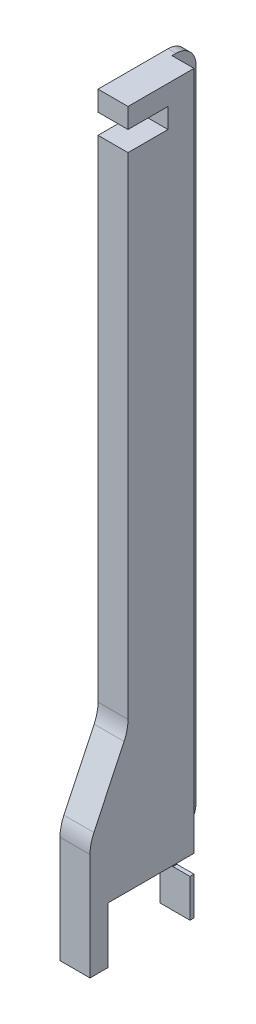
SolidWorks part; units mm, degrees
ref_plane "정면" through (0, 0, 0) normal (0, 0, 1) x (1, 0, 0)
ref_plane "윗면" through (0, 0, 0) normal (0, 1, 0) x (1, 0, 0)
ref_plane "우측면" through (0, 0, 0) normal (1, 0, 0) x (0, 0, -1)
sketch "스케치1" plane through (0, 0, 0) normal (0, 0, 1) x (1, 0, 0)
  line L0 (-318.5049, 0) -> (318.5049, 0) construction
  line L1 (0, 0) -> (0, -258.8265) construction
  line L2 (-168, 0) -> (168, 0)
  line L3 (-168, -20) -> (168, -20)
  line L4 (168, -20) -> (168, 0) construction
  line L5 (168, -20) -> (168, -340)
  line L6 (172, -340) -> (172, 0)
  line L7 (168, 0) -> (183, 0)
  line L8 (183, 0) -> (183, -340)
  line L9 (183, -340) -> (168, -340)
  line L10 (-168, -20) -> (-168, 0) construction
  line L11 (-183, -340) -> (-168, -340)
  line L12 (-183, 0) -> (-183, -340)
  line L13 (-168, 0) -> (-183, 0)
  line L14 (-172, -340) -> (-172, 0)
  line L15 (-168, -20) -> (-168, -340)
  line L16 (168, -20) -> (168, 0)
  line L17 (-168, -20) -> (-168, 0)
  point P14 (0, -20)
  dimension "D1" = 168
  dimension "D2" = 20
  dimension "D3" = 4
  dimension "D4" = 340
  dimension "D5" = 15
extrude "보스-돌출1" add sketch "스케치1" along normal blind 26 contours L3 L5 L9 L8 L7 L2 L13 L12 L11 L15
extrude "보스-돌출2" add sketch "스케치1<4>" against normal blind 19 contours L16 L5 L9 L6 L7 | L15 L17 L13 L14 L11 region at (-170, -170, 0) region at (170, -170, 0)
sketch "스케치1<4>" plane through (0, 0, 0) normal (0, 0, 1) x (1, 0, 0) same geometry as "스케치1"
fillet "필렛1" radius 10 4 edges at (-170, 0, -19) (170, 0, -19) (170, -340, -19) (-170, -340, -19)
sketch "스케치2" plane through (172, 0, 0) normal (1, 0, 0) x (0, 0, -1)
  line L0 (14, -340) -> (14, 0)
  line L1 (12, 0) -> (12, -340)
  line L4 (19, -330) -> (19, -10)
  line L5 (9, 0) -> (0, 0)
  line L6 (0, 0) -> (0, -340)
  line L7 (0, -340) -> (9, -340)
  line L8 (19, -330) -> (19, -10)
  line L9 (9, 0) -> (0, 0)
  line L10 (0, 0) -> (0, -340)
  line L11 (0, -340) -> (9, -340)
  arc A2 (19, -10) -> (9, 0) centre (9, -10) ccw
  arc A3 (9, -340) -> (19, -330) centre (9, -330) ccw
  arc A4 (19, -10) -> (9, 0) centre (9, -10) ccw
  arc A5 (9, -340) -> (19, -330) centre (9, -330) ccw
  dimension "D2" = 5
  dimension "D3" = 2
  dimension "D1" = 0
sketch "스케치3" plane through (168, 0, 0) normal (-1, 0, 0) x (0, 0, 1)
  line L0 (-12, 0) -> (-12, -340) construction
  line L1 (-14, -340) -> (-14, 0) construction
  line L2 (-12, 0) -> (-12, -340)
  line L3 (-14, -340) -> (-14, 0)
  line L4 (-19, -10) -> (-19, -330)
  line L5 (0, 0) -> (-9, 0)
  line L6 (0, -340) -> (0, 0)
  line L7 (-9, -340) -> (0, -340)
  line L8 (-19, -10) -> (-19, -330)
  line L9 (0, 0) -> (-9, 0)
  line L10 (0, -340) -> (0, 0)
  line L11 (-9, -340) -> (0, -340)
  arc A2 (-9, 0) -> (-19, -10) centre (-9, -10) ccw
  arc A3 (-19, -330) -> (-9, -340) centre (-9, -330) ccw
  arc A4 (-9, 0) -> (-19, -10) centre (-9, -10) ccw
  arc A5 (-19, -330) -> (-9, -340) centre (-9, -330) ccw
  dimension "D1" = 0
sketch "스케치5" plane through (0, 0, 0) normal (0, 1, 0) x (1, 0, 0)
  line L0 (-7, 0) -> (-7, -26)
  line L1 (7, 0) -> (7, -26)
  line L2 (-168, 0) -> (-168, -6)
  line L3 (-168, -6) -> (-7, -6)
  line L4 (7, -6) -> (168, -6)
  line L5 (168, -6) -> (168, 0)
  line L12 (-168, 0) -> (-168, 9)
  line L13 (-168, 9) -> (-172, 9)
  line L14 (-172, 9) -> (-172, 0)
  line L15 (-172, 0) -> (-183, 0)
  line L16 (-183, 0) -> (-183, -26)
  line L17 (-183, -26) -> (183, -26)
  line L18 (183, -26) -> (183, 0)
  line L19 (183, 0) -> (172, 0)
  line L20 (172, 0) -> (172, 9)
  line L21 (172, 9) -> (168, 9)
  line L22 (168, 9) -> (168, 0)
  line L23 (168, 0) -> (-168, 0)
  line L24 (-168, 0) -> (-168, 9)
  line L25 (-168, 9) -> (-172, 9)
  line L26 (-172, 9) -> (-172, 0)
  line L27 (-172, 0) -> (-183, 0)
  line L28 (-183, 0) -> (-183, -26)
  line L29 (-183, -26) -> (183, -26)
  line L30 (183, -26) -> (183, 0)
  line L31 (183, 0) -> (172, 0)
  line L32 (172, 0) -> (172, 9)
  line L33 (172, 9) -> (168, 9)
  line L34 (168, 9) -> (168, 0)
  line L35 (168, 0) -> (-168, 0)
  line M27 (168, 0) -> (-168, 0)
  dimension "D2" = 7
  dimension "D3" = 7
  dimension "D4" = 6
  dimension "D1" = 0
extrude "컷-돌출1" cut sketch "스케치5" against normal blind 52 contours L2 L3 L0 M27 | L4 L5 L1 M27 region at (-87.5, 0, 3) region at (87.5, 0, 3)
extrude "보스-돌출4" add sketch "스케치1<5>" against normal blind 7 contours L9 L8 L7 L6 | L11 L14 L13 L12 region at (-177.5, -170, 0) region at (177.5, -170, 0)
sketch "스케치1<5>" plane through (0, 0, 0) normal (0, 0, 1) x (1, 0, 0) same geometry as "스케치1"
sketch "스케치6" plane through (0, -340, 0) normal (0, -1, 0) x (1, 0, 0)
  line L0 (-172, -7) -> (-126.7636, -7) construction
  line L1 (-172, -7) -> (-168, -7)
  line L2 (-168, -7) -> (-168, -5)
  line L3 (-168, -5) -> (-174.5, -5)
  line L4 (-174.5, -5) -> (-174.5, -7)
  line L5 (-181.1, -7) -> (-181.1, -5)
  line L6 (-172, -7) -> (-172, -9)
  line L7 (-172, -9) -> (-168, -9)
  line L8 (-168, -9) -> (-168, 26)
  line L9 (-168, 26) -> (-183, 26)
  line L10 (-183, 26) -> (-183, -7)
  line L11 (-183, -7) -> (-172, -7)
  line L12 (-172, -7) -> (-172, -9)
  line L13 (-172, -9) -> (-168, -9)
  line L14 (-168, -9) -> (-168, 26)
  line L15 (-168, 26) -> (-183, 26)
  line L16 (-183, 26) -> (-183, -7)
  line L17 (-183, -7) -> (-172, -7)
  line L18 (-181.1, -5) -> (-183, -5)
  line L19 (-181.1, -5) -> (-174.5, -5)
  line L20 (-168, 26) -> (-168, 36)
  line L21 (-168, 36) -> (-183, 36)
  line L22 (-183, 36) -> (-183, 26)
  line L23 (-168, 36) -> (-168, 45)
  line L24 (-168, 45) -> (-183, 45)
  line L25 (-183, 45) -> (-183, 36)
  line M14 (-168, -9) -> (-168, 26)
  line M15 (-168, 26) -> (-183, 26)
  line M17 (-183, -7) -> (-172, -7)
  dimension "D2" = 6.5
  dimension "D3" = 2
  dimension "D4" = 6.6
  dimension "D5" = 41
  dimension "D6" = 9
  dimension "D1" = 0
extrude "보스-돌출5" add sketch "스케치6" along normal blind 28 contours L5 L18 L16 M17 | L19 L5 L4 M17 | L3 L4 L1 M17 M14 region at (-171.25, -340, -6) region at (-177.8, -340, -6) region at (-182.05, -340, -6)
extrude "컷-돌출2" cut sketch "스케치6<3>" along normal blind 5 contours L19 L5 L4 M17 region at (-177.8, -340, -6)
sketch "스케치6<3>" plane through (0, -340, 0) normal (0, -1, 0) x (1, 0, 0) same geometry as "스케치6"
fillet "필렛2" radius 20 1 edges at (-170, -340, -7)
extrude "보스-돌출6" add sketch "스케치6<4>" against normal blind 30 contours L21 L22 L20 M15 | L24 L25 L21 L23 region at (-175.5, -340, 31) region at (-175.5, -340, 40.5)
sketch "스케치6<4>" plane through (0, -340, 0) normal (0, -1, 0) x (1, 0, 0) same geometry as "스케치6"
extrude "보스-돌출7" add sketch "스케치6<5>" along normal blind 28 contours L24 L25 L21 L23 region at (-175.5, -340, 40.5)
sketch "스케치6<5>" plane through (0, -340, 0) normal (0, -1, 0) x (1, 0, 0) same geometry as "스케치6"
sketch "스케치9" plane through (-183, 0, 0) normal (-1, 0, 0) x (0, 0, 1)
  line L0 (45, -310) -> (26, -270)
  line L1 (26, 0) -> (26, -310) construction
  line L12 (26, 0) -> (-7, 0)
  line L13 (-7, 0) -> (-7, -368)
  line L14 (-7, -368) -> (-5, -368)
  line L15 (-5, -368) -> (-5, -340)
  line L16 (-5, -340) -> (36, -340)
  line L17 (36, -340) -> (36, -368)
  line L18 (36, -368) -> (45, -368)
  line L19 (45, -368) -> (45, -310)
  line L20 (45, -310) -> (26, -310)
  line L21 (26, -310) -> (26, 0)
  line L22 (26, 0) -> (-7, 0)
  line L23 (-7, 0) -> (-7, -368)
  line L24 (-7, -368) -> (-5, -368)
  line L25 (-5, -368) -> (-5, -340)
  line L26 (-5, -340) -> (36, -340)
  line L27 (36, -340) -> (36, -368)
  line L28 (36, -368) -> (45, -368)
  line L29 (45, -368) -> (45, -310)
  line L30 (45, -310) -> (26, -310)
  line L31 (26, -310) -> (26, 0)
  line M19 (45, -310) -> (26, -310)
  line M20 (26, -310) -> (26, 0)
  dimension "D2" = 40
  dimension "D1" = 0
extrude "보스-돌출8" add sketch "스케치9" against normal blind 15 contours L0 M19 M20 region at (-183, -296.6667, 32.3333)
fillet "필렛3" radius 20 2 edges at (-175.5, -270, 26) (-175.5, -310, 45)
mirror "대칭 복사2" about plane through (0, 0, 0) normal (1, 0, 0) of "보스-돌출5", "컷-돌출2", "필렛3", "보스-돌출6", "보스-돌출7", "보스-돌출8"
fillet "필렛4" radius 20 1 edges at (170, -340, -7)
sketch "스케치10" plane through (183, 0, 0) normal (1, 0, 0) x (0, 0, -1)
  line L0 (-27.9344, -274.0725) -> (-43.0656, -305.9275) construction
  line L1 (-45, -314.5086) -> (-45, -368) construction
  line L2 (-45, -368) -> (-36, -368) construction
  line L3 (-36, -368) -> (-36, -340) construction
  line L4 (-36, -340) -> (5, -340) construction
  line L5 (5, -340) -> (5, -368) construction
  line L6 (5, -368) -> (7, -368) construction
  line L7 (7, -368) -> (7, -354) construction
  line L8 (19, -330) -> (19, -10) construction
  line L9 (9, 0) -> (-6, 0) construction
  line L10 (-6, 0) -> (-6, -20) construction
  line L11 (-6, -20) -> (-26, -20) construction
  line L12 (-26, -20) -> (-26, -265.4914) construction
  line L13 (-27.9344, -274.0725) -> (-43.0656, -305.9275) construction
  line L14 (-45, -314.5086) -> (-45, -368) construction
  line L15 (-45, -368) -> (-36, -368) construction
  line L16 (-36, -368) -> (-36, -340) construction
  line L17 (-36, -340) -> (5, -340) construction
  line L18 (5, -340) -> (5, -368) construction
  line L19 (5, -368) -> (7, -368) construction
  line L20 (7, -368) -> (7, 0) construction
  line L21 (7, 0) -> (-26, 0) construction
  line L22 (-26, 0) -> (-26, -265.4914) construction
  line L23 (-27.9344, -274.0725) -> (-43.0656, -305.9275)
  line L24 (-45, -314.5086) -> (-45, -368)
  line L25 (-45, -368) -> (-36, -368)
  line L26 (-36, -368) -> (-36, -340)
  line L27 (-36, -340) -> (5, -340)
  line L28 (5, -340) -> (5, -368)
  line L29 (5, -368) -> (7, -368)
  line L30 (7, -368) -> (7, -354)
  line L31 (19, -330) -> (19, -10)
  line L32 (9, 0) -> (-6, 0)
  line L33 (-6, 0) -> (-6, -20)
  line L34 (-6, -20) -> (-26, -20)
  line L35 (-26, -20) -> (-26, -265.4914)
  line L36 (-27.9344, -274.0725) -> (-43.0656, -305.9275)
  line L37 (-45, -314.5086) -> (-45, -368)
  line L38 (-45, -368) -> (-36, -368)
  line L39 (-36, -368) -> (-36, -340)
  line L40 (-36, -340) -> (5, -340)
  line L41 (5, -340) -> (5, -368)
  line L42 (5, -368) -> (7, -368)
  line L43 (7, -368) -> (7, 0)
  line L44 (7, 0) -> (-26, 0)
  line L45 (-26, 0) -> (-26, -265.4914)
  line L46 (-26, -10) -> (-6, -10)
  arc A0 (-43.0656, -305.9275) -> (-45, -314.5086) centre (-25, -314.5086) ccw construction
  arc A1 (15, -338) -> (7, -354) centre (27, -354) ccw construction
  arc A2 (15, -338) -> (19, -330) centre (9, -330) ccw construction
  arc A3 (19, -10) -> (9, 0) centre (9, -10) ccw construction
  arc A4 (-27.9344, -274.0725) -> (-26, -265.4914) centre (-46, -265.4914) ccw construction
  arc A5 (-43.0656, -305.9275) -> (-45, -314.5086) centre (-25, -314.5086) ccw construction
  arc A6 (-27.9344, -274.0725) -> (-26, -265.4914) centre (-46, -265.4914) ccw construction
  arc A7 (-43.0656, -305.9275) -> (-45, -314.5086) centre (-25, -314.5086) ccw
  arc A8 (15, -338) -> (7, -354) centre (27, -354) ccw
  arc A9 (15, -338) -> (19, -330) centre (9, -330) ccw
  arc A10 (19, -10) -> (9, 0) centre (9, -10) ccw
  arc A11 (-27.9344, -274.0725) -> (-26, -265.4914) centre (-46, -265.4914) ccw
  arc A12 (-43.0656, -305.9275) -> (-45, -314.5086) centre (-25, -314.5086) ccw
  arc A13 (-27.9344, -274.0725) -> (-26, -265.4914) centre (-46, -265.4914) ccw
sketch "스케치11" plane through (168, 0, 0) normal (-1, 0, 0) x (0, 0, 1)
  line L10 (43.0656, -305.9275) -> (27.9344, -274.0725)
  line L11 (45, -368) -> (45, -314.5086)
  line L12 (36, -368) -> (45, -368)
  line L13 (45, -368) -> (45, -314.5086)
  line L14 (43.0656, -305.9275) -> (27.9344, -274.0725)
  line L15 (26, -265.4914) -> (26, -20)
  line L16 (26, -20) -> (6, -20)
  line L17 (6, -20) -> (6, 0)
  line L18 (6, 0) -> (-9, 0)
  line L19 (-19, -10) -> (-19, -330)
  line L20 (-7, -354) -> (-7, -368)
  line L21 (-7, -368) -> (-5, -368)
  line L22 (-5, -368) -> (-5, -340)
  line L23 (-5, -340) -> (36, -340)
  line L24 (36, -340) -> (36, -368)
  line L25 (36, -368) -> (45, -368)
  line L26 (45, -368) -> (45, -314.5086)
  line L27 (43.0656, -305.9275) -> (27.9344, -274.0725)
  line L28 (26, -265.4914) -> (26, -20)
  line L29 (26, -20) -> (6, -20)
  line L30 (6, -20) -> (6, 0)
  line L31 (6, 0) -> (-9, 0)
  line L32 (-19, -10) -> (-19, -330)
  line L33 (-7, -354) -> (-7, -368)
  line L34 (-7, -368) -> (-5, -368)
  line L35 (-5, -368) -> (-5, -340)
  line L36 (-5, -340) -> (36, -340)
  line L37 (36, -340) -> (36, -368)
  line L38 (36, -368) -> (45, -368)
  line L39 (36, -340) -> (36, -368)
  line L40 (-5, -340) -> (36, -340)
  line L41 (-5, -368) -> (-5, -340)
  line L42 (-7, -368) -> (-5, -368)
  line L43 (-7, 0) -> (-7, -368)
  line L44 (26, 0) -> (-7, 0)
  line L45 (26, -265.4914) -> (26, 0)
  line L46 (43.0656, -305.9275) -> (27.9344, -274.0725)
  line L47 (45, -368) -> (45, -314.5086)
  line L48 (36, -368) -> (45, -368)
  line L49 (36, -340) -> (36, -368)
  line L50 (-5, -340) -> (36, -340)
  line L51 (-5, -368) -> (-5, -340)
  line L52 (-7, -368) -> (-5, -368)
  line L53 (-7, 0) -> (-7, -368)
  line L54 (26, 0) -> (-7, 0)
  line L55 (26, -265.4914) -> (26, 0)
  arc A2 (45, -314.5086) -> (43.0656, -305.9275) centre (25, -314.5086) ccw
  arc A3 (26, -265.4914) -> (27.9344, -274.0725) centre (46, -265.4914) ccw
  arc A4 (45, -314.5086) -> (43.0656, -305.9275) centre (25, -314.5086) ccw
  arc A5 (45, -314.5086) -> (43.0656, -305.9275) centre (25, -314.5086) ccw
  arc A6 (26, -265.4914) -> (27.9344, -274.0725) centre (46, -265.4914) ccw
  arc A7 (-9, 0) -> (-19, -10) centre (-9, -10) ccw
  arc A8 (-19, -330) -> (-15, -338) centre (-9, -330) ccw
  arc A9 (-7, -354) -> (-15, -338) centre (-27, -354) ccw
  arc A10 (45, -314.5086) -> (43.0656, -305.9275) centre (25, -314.5086) ccw
  arc A11 (26, -265.4914) -> (27.9344, -274.0725) centre (46, -265.4914) ccw
  arc A12 (-9, 0) -> (-19, -10) centre (-9, -10) ccw
  arc A13 (-19, -330) -> (-15, -338) centre (-9, -330) ccw
  arc A14 (-7, -354) -> (-15, -338) centre (-27, -354) ccw
  arc A15 (26, -265.4914) -> (27.9344, -274.0725) centre (46, -265.4914) ccw
  line M31 (45, -368) -> (45, -314.5086)
  arc M32 (45, -314.5086) -> (43.0656, -305.9275) centre (25, -314.5086) ccw
  line M33 (43.0656, -305.9275) -> (27.9344, -274.0725)
  arc M34 (27.9344, -274.0725) -> (26, -265.4914) centre (46, -265.4914) cw
  line M35 (26, -265.4914) -> (26, -20)
  line M36 (26, -20) -> (6, -20)
  line M37 (6, -20) -> (6, 0)
  line M38 (6, 0) -> (-9, 0)
  arc M39 (-9, 0) -> (-19, -10) centre (-9, -10) ccw
  line M40 (-19, -10) -> (-19, -330)
  arc M41 (-19, -330) -> (-15, -338) centre (-9, -330) ccw
  arc M42 (-15, -338) -> (-7, -354) centre (-27, -354) cw
  line M43 (-7, -354) -> (-7, -368)
  line M44 (-7, -368) -> (-5, -368)
  line M45 (-5, -368) -> (-5, -340)
  line M46 (-5, -340) -> (36, -340)
  line M47 (36, -340) -> (36, -368)
  line M48 (36, -368) -> (45, -368)
  dimension "D1" = 0
  dimension "D2" = 0
extrude "컷-돌출3" cut sketch "스케치11" along normal blind 617 contours L53 M38 M43 M44 M45 M46 M47 M48 M31 M32 M33 M34 M35 M36 M37 | L55 L54 M36 M37 | L53 L31 M39 M40 M41 M42 region at (168, -191.2863, 11.8028) region at (168, -10, 16) region at (168, -171.1237, -12.9334)
extrude "컷-돌출4" cut sketch "스케치10" against normal blind 617 contours L46 L45 L34 L33 region at (183, -15, 16)
sketch "스케치12" plane through (168, 0, 0) normal (-1, 0, 0) x (0, 0, 1)
  line L0 (18, -203) -> (18, -163)
  line L1 (18, -163) -> (10, -163)
  line L2 (10, -163) -> (10, -203)
  line L3 (10, -203) -> (-19, -203)
  line L4 (18.2, -203) -> (18.2, -162.8)
  line L5 (18.2, -162.8) -> (9.8, -162.8)
  line L6 (9.8, -162.8) -> (9.8, -203)
  line L15 (26, -183) -> (-19, -183) construction
  line L16 (26, -203) -> (18, -203)
  line L18 (-7, 0) -> (-9, 0)
  line L19 (-7, -354) -> (-7, 0)
  line L20 (-19, -10) -> (-19, -330)
  line L21 (-7, 0) -> (-9, 0)
  line L22 (-7, -354) -> (-7, 0)
  line L23 (-19, -10) -> (-19, -330)
  line L30 (6, -10) -> (26, -10)
  line L31 (26, -10) -> (26, 0)
  line L32 (26, 0) -> (-9, 0)
  line L33 (-19, -10) -> (-19, -330)
  line L34 (-7, -354) -> (-7, -368)
  line L35 (-7, -368) -> (-5, -368)
  line L36 (-5, -368) -> (-5, -340)
  line L37 (-5, -340) -> (36, -340)
  line L38 (36, -340) -> (36, -368)
  line L39 (36, -368) -> (45, -368)
  line L40 (45, -368) -> (45, -314.5086)
  line L41 (43.0656, -305.9275) -> (27.9344, -274.0725)
  line L42 (26, -265.4914) -> (26, -20)
  line L43 (26, -20) -> (6, -20)
  line L44 (6, -20) -> (6, -10)
  line L45 (6, -10) -> (26, -10)
  line L46 (26, -10) -> (26, 0)
  line L47 (26, 0) -> (-9, 0)
  line L48 (-19, -10) -> (-19, -330)
  line L49 (-7, -354) -> (-7, -368)
  line L50 (-7, -368) -> (-5, -368)
  line L51 (-5, -368) -> (-5, -340)
  line L52 (-5, -340) -> (36, -340)
  line L53 (36, -340) -> (36, -368)
  line L54 (36, -368) -> (45, -368)
  line L55 (45, -368) -> (45, -314.5086)
  line L56 (43.0656, -305.9275) -> (27.9344, -274.0725)
  line L57 (26, -265.4914) -> (26, -20)
  line L58 (26, -20) -> (6, -20)
  line L59 (6, -20) -> (6, -10)
  arc A8 (-7, -354) -> (-15, -338) centre (-27, -354) ccw
  arc A9 (-19, -330) -> (-15, -338) centre (-9, -330) ccw
  arc A10 (-9, 0) -> (-19, -10) centre (-9, -10) ccw
  arc A11 (-19, -330) -> (-15, -338) centre (-9, -330) ccw
  arc A12 (-7, -354) -> (-15, -338) centre (-27, -354) ccw
  arc A13 (45, -314.5086) -> (43.0656, -305.9275) centre (25, -314.5086) ccw
  arc A14 (26, -265.4914) -> (27.9344, -274.0725) centre (46, -265.4914) ccw
  arc A15 (-9, 0) -> (-19, -10) centre (-9, -10) ccw
  arc A16 (-19, -330) -> (-15, -338) centre (-9, -330) ccw
  arc A17 (-7, -354) -> (-15, -338) centre (-27, -354) ccw
  arc A18 (45, -314.5086) -> (43.0656, -305.9275) centre (25, -314.5086) ccw
  arc A19 (26, -265.4914) -> (27.9344, -274.0725) centre (46, -265.4914) ccw
  arc A20 (-9, 0) -> (-19, -10) centre (-9, -10) ccw
  arc A21 (-7, -354) -> (-15, -338) centre (-27, -354) ccw
  arc A22 (-19, -330) -> (-15, -338) centre (-9, -330) ccw
  arc A23 (-9, 0) -> (-19, -10) centre (-9, -10) ccw
  dimension "D3" = 185
  dimension "D4" = 8
  dimension "D5" = 8
  dimension "D6" = 20
  dimension "D7" = 20
  dimension "D1" = 0
  dimension "D2" = 0
  dimension "D8" = 0.2
sketch "스케치13" plane through (183, 0, 0) normal (1, 0, 0) x (0, 0, -1)
  line L0 (5, -340) -> (7, -340)
  line L1 (7, 0) -> (7, -368) construction
  line L2 (7, -340) -> (7, -349)
  line L3 (7, -349) -> (5, -349)
  line L4 (5, -368) -> (5, -340) construction
  line L5 (5, -349) -> (5, -340)
  dimension "D1" = 9
extrude "컷-돌출8" cut sketch "스케치13" against normal blind 8.5
